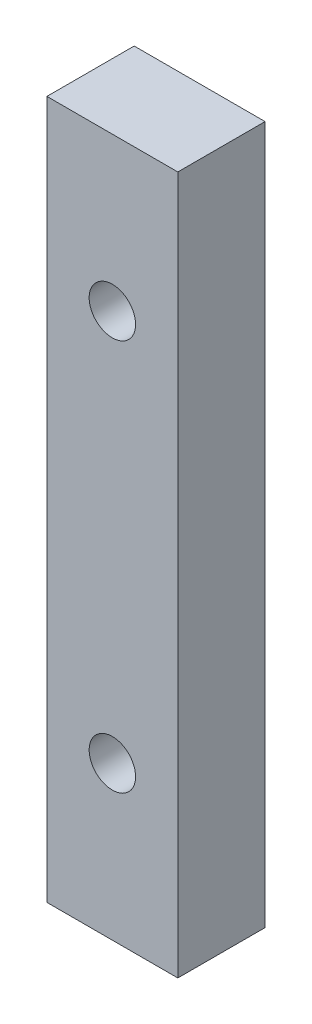
SolidWorks part; units mm, degrees
ref_plane "Front Plane" through (0, 0, 0) normal (0, 0, 1) x (1, 0, 0)
ref_plane "Top Plane" through (0, 0, 0) normal (0, 1, 0) x (1, 0, 0)
ref_plane "Right Plane" through (0, 0, 0) normal (1, 0, 0) x (0, 0, -1)
sketch "Sketch1" plane through (0, 0, 0) normal (0, 0, 1) x (1, 0, 0)
  line L0 (-9.525, 0) -> (9.525, 0) construction
  line L1 (-9.525, 50.8) -> (9.525, 50.8)
  line L2 (-9.525, 50.8) -> (-9.525, -50.8)
  line L3 (-9.525, -50.8) -> (9.525, -50.8)
  line L4 (9.525, 50.8) -> (9.525, -50.8)
  line L5 (0, -50.8) -> (0, 50.8) construction
  point P8 (0, 0)
  dimension "D1" = 19.05
  dimension "D2" = 101.6
extrude "Boss-Extrude1" add sketch "Sketch1" along normal blind 12.7
hole_wizard "1/4 Clearance Hole1" positions "Sketch2" profile "Sketch3" hole size "1/4" standard "ANSI Inch" end condition through all
sketch "Sketch2" plane through (0, 0, 12.7) normal (0, 0, 1) x (1, 0, 0)
  line L0 (0, -50.8) -> (0, 50.8) construction
  line L2 (-9.525, 0) -> (9.525, 0) construction
  line L4 (-9.525, 50.8) -> (-9.525, -50.8) construction
  line L5 (9.525, -50.8) -> (9.525, 50.8) construction
  point P0 (0, 28.5)
  point P2 (0, -28.5)
  point P17 (0, 0)
  dimension "D1" = 57
sketch "Sketch3" plane through (0, 28.5, 12.7) normal (1, 0, 0) x (0, -1, 0)
  line L0 (0, 0) -> (0, 12.7)
  line L1 (0, 12.7) -> (3.3782, 12.7)
  line L2 (3.3782, 12.7) -> (3.3782, 0)
  line L5 (3.3782, 0) -> (0, 0)
  line L11 (0, -6.35) -> (0, 107.95) construction
  dimension "Thru Hole Dia." = 6.7564
  dimension "Thru Hole Depth" = 12.7
